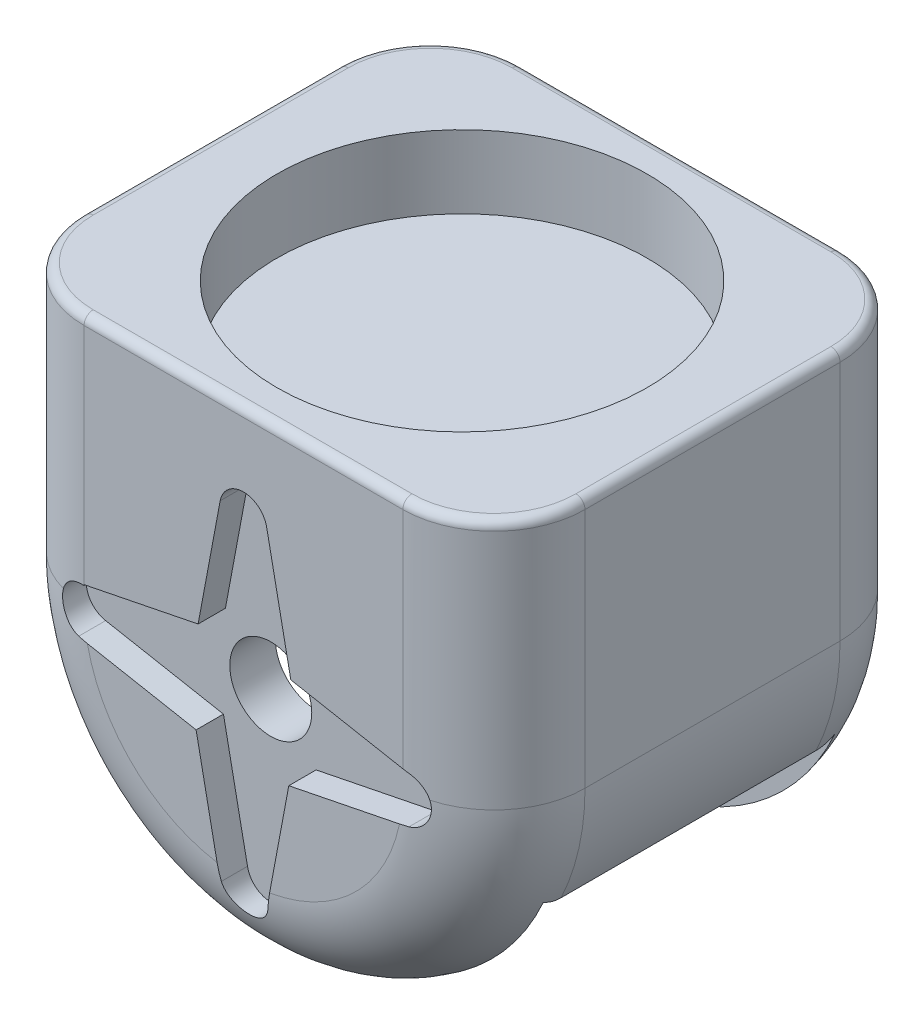
SolidWorks part; units mm, degrees
other "Markup1"
sketch "Sketch6" plane through (32.5, 40, -30) normal (0.2507, 0.8626, -0.4394) x (-0.8645, -0.0047, -0.5026)
ref_plane "Front Plane" through (0, 0, 0) normal (0, 0, 1) x (1, 0, 0)
ref_plane "Top Plane" through (0, 0, 0) normal (0, 1, 0) x (1, 0, 0)
ref_plane "Right Plane" through (0, 0, 0) normal (1, 0, 0) x (0, 0, -1)
sketch "Sketch1" plane through (0, 0, 0) normal (0, 1, 0) x (1, 0, 0)
  circle A0 centre (0, 0) radius 20.325
  dimension "D1" = 40.65
sketch "Sketch2" plane through (0, 0, 0) normal (0, 0, 1) x (1, 0, 0)
  line L0 (-27.5, -27.5) -> (-27.5, 0)
  line L1 (-27.5, 0) -> (27.5, 0)
  line L2 (27.5, 0) -> (27.5, -27.5)
  arc A0 (-27.5, -27.5) -> (27.5, -27.5) centre (0, -27.5) ccw
  dimension "D1" = 55
extrude "Boss-Extrude1" add sketch "Sketch2" along normal mid plane 48 separate body
sketch "Sketch3" plane through (0, 0, 0) normal (0, 1, 0) x (1, 0, 0)
  line L0 (-18.5, 0) -> (-20.325, 0) construction
  circle A0 centre (0, 0) radius 20.325
  circle A1 centre (0, 0) radius 18.5
  point P21 (0, 0)
  dimension "D3" = 40.65
  dimension "D4" = 37
extrude "Cut-Extrude1" cut sketch "Sketch3" against normal blind 8 contours L0 | L0 | A1 A0 | A0 region at (-19.7501, 0, 0)
sketch "Sketch5" [suppressed] plane through (0, 0, 0) normal (0, 0, 1) x (1, 0, 0)
  line L0 (-0.0105, 0) -> (-27.325, 0)
  line L1 (-27.325, 40) -> (-27.325, 0) construction
  line L2 (-27.325, 0) -> (-27.325, -9.0775)
  arc A1 (-0.0105, 0) -> (-27.325, -9.0775) centre (-0.0105, -45.6339) ccw
fillet "Fillet1" radius 10 6 edges at (27.5, -13.75, -24) (0, -55, -24) (27.5, -13.75, 24) (0, -55, 24) (-27.5, -13.75, -24) (-27.5, -13.75, 24)
fillet "Fillet5" radius 1 8 edges at (24.5711, 0, 21.0711) (0, 0, 24) (0, 0, -24) (24.5711, 0, -21.0711) (-24.5711, 0, 21.0711) (-24.5711, 0, -21.0711) (27.5, 0, 0) (-27.5, 0, 0)
sketch "Sketch7" plane through (0, 0, 0) normal (0, 0, 1) x (1, 0, 0)
  line L0 (-0.0113, -11.8764) -> (-25.0113, -11.8764)
  line L1 (-25.0113, -11.8764) -> (-25.0113, -36.8764)
  line L6 (24.9887, -36.8764) -> (24.9887, -11.8764)
  line L7 (24.9887, -11.8764) -> (-0.0113, -11.8764)
  arc A0 (-25.0113, -36.8764) -> (24.9887, -36.8764) centre (-0.0113, -36.8764) ccw
  dimension "D1" = 50
extrude "Cut-Extrude2" cut sketch "Sketch7" against normal mid plane 32
sketch "Sketch10" plane through (0, 0, 24) normal (0, 0, 1) x (1, 0, 0)
  circle A0 centre (0, -28.3193) radius 4.5
  dimension "D1" = 9
extrude "Cut-Extrude4" cut sketch "Sketch10" against normal blind 75
sketch "Sketch11" plane through (0, 0, 24) normal (0, 0, 1) x (1, 0, 0)
  line L0 (0, -8.8005) -> (0, -43.05) construction
  line L1 (-2.5555, -10.1906) -> (-4.9781, -23.1217)
  line L2 (-6.912, -28.3193) -> (8.6285, -28.3193) construction
  line L3 (-2.5555, -46.4481) -> (-5.1976, -33.2974)
  line L4 (2.5555, -46.4481) -> (4.9781, -33.5169)
  line L5 (2.5555, -10.1906) -> (5.1976, -23.3413)
  line L6 (18.1288, -25.7638) -> (5.1976, -23.3413)
  line L7 (18.1288, -30.8749) -> (4.9781, -33.5169)
  line L8 (2.5555, -46.4481) -> (4.9781, -33.5169)
  line L9 (-2.5555, -46.4481) -> (-5.1976, -33.2974)
  line L10 (-18.1288, -30.8749) -> (-5.1976, -33.2974)
  line L11 (-18.1288, -25.7638) -> (-4.9781, -23.1217)
  line L12 (-5.1976, -33.2974) -> (-18.1288, -30.8749)
  line L13 (4.9781, -33.5169) -> (18.1288, -30.8749)
  circle A0 centre (0, -28.3193) radius 5.85
  circle A1 centre (0, -10.6693) radius 2.6
  circle A2 centre (0, -45.9693) radius 2.6
  circle A3 centre (-17.65, -28.3193) radius 2.6
  circle A4 centre (0, -10.6693) radius 2.6
  circle A5 centre (17.65, -28.3193) radius 2.6
  point P41 (0, -28.3193)
  line M8 (17.5, -27.5) -> (17.5, -1)
  line M10 (-17.5, -1) -> (-17.5, -27.5)
  arc M11 (-17.5, -27.5) -> (17.5, -27.5) centre (0, -27.5) ccw
  dimension "D1" = 11.7
  dimension "D2" = 5.2
  dimension "D3" = 5.2
  dimension "D4" = 17.65
  dimension "D5" = 17.65
  dimension "D6" = 4
extrude "Cut-Extrude5" cut sketch "Sketch11" against normal blind 3 contours A3 M11 M10 | A3 M10 M11 | A5 L6 L5 A1 L1 L11 A3 L10 L3 A2 L4 L7 A0 M8 M10 M11 | A3 L10 M11 | A5 M8 M11 | A5 M8 M11 | A1 | A2 L4 M11 | A2 M11 | A2 M11 | A2 L3 M11 | A5 L7 M11 | A5 L6 M8 | A3 | A0 region at (-0.2859, -13.7486, 24) region at (0, -10.6693, 24) region at (-18.6323, -28.3746, 24) region at (-16.4278, -28.2506, 24) region at (17.6578, -25.6989, 24) region at (-17.3977, -30.9577, 24) region at (18.6323, -28.3746, 24) region at (16.4278, -28.2506, 24) region at (17.4044, -30.9623, 24) region at (-2.6417, -45.2209, 24) region at (0, -46.5454, 24) region at (0, -44.2967, 24) region at (2.6329, -45.2141, 24)
sketch "Sketch12" plane through (0, 0, -24) normal (0, 0, -1) x (-1, 0, 0)
  circle A0 centre (0, -28.3193) radius 7.5
  dimension "D1" = 15
extrude "Cut-Extrude6" cut sketch "Sketch12" against normal blind 10
